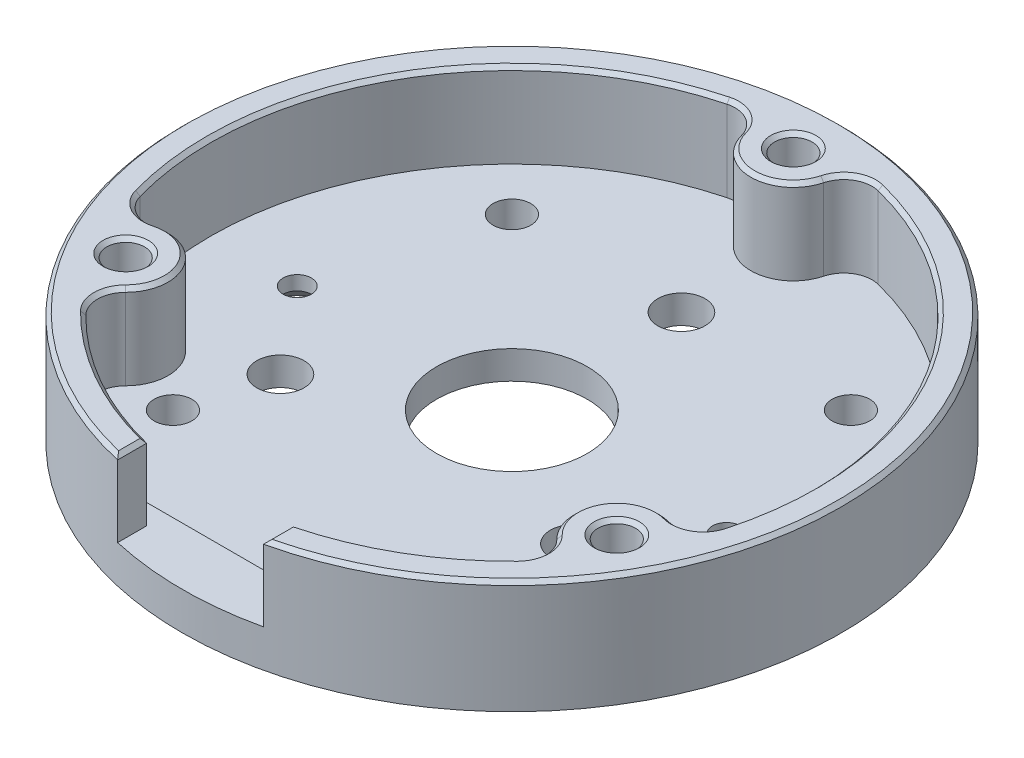
SolidWorks part; units mm, degrees
ref_plane "Спереди" through (0, 0, 0) normal (0, 0, 1) x (1, 0, 0)
ref_plane "Сверху" through (0, 0, 0) normal (0, 1, 0) x (1, 0, 0)
ref_plane "Справа" through (0, 0, 0) normal (1, 0, 0) x (0, 0, -1)
other "Configuration Table"
sketch "Эскиз1" plane through (0, 0, 0) normal (0, 1, 0) x (1, 0, 0)
  circle A0 centre (0, 0) radius 35
  circle A1 centre (0, 0) radius 8
  dimension "D1" = 16
  dimension "D2" = 70
extrude "Бобышка-Вытянуть1" add sketch "Эскиз1" along normal blind 3
sketch "Эскиз2" plane through (0, 3, 0) normal (0, 1, 0) x (1, 0, 0)
  circle A17 centre (-0.1137, 30) radius 2
  circle A18 centre (26.0376, -14.9016) radius 2
  circle A19 centre (-25.9239, -15.0984) radius 2
  circle A21 centre (0, 0) radius 35
  arc A22 (-8.1171, 30.9534) -> (-30.8001, -8.6807) centre (0, 0) ccw
  arc A23 (-4.4591, 28.8309) -> (4.2406, 28.8639) centre (-0.1137, 30) ccw
  arc A24 (27.1979, -10.5537) -> (22.8766, -18.1044) centre (26.0376, -14.9016) ccw
  arc A25 (-22.7387, -18.2772) -> (-27.1171, -10.7595) centre (-25.9239, -15.0984) ccw
  arc A26 (30.865, -8.4471) -> (7.8823, 31.014) centre (0, 0) ccw
  arc A27 (-22.7479, -22.5063) -> (22.9178, -22.3333) centre (0, 0) ccw
  arc A28 (-27.1171, -10.7595) -> (-30.8001, -8.6807) centre (-27.9126, -7.8669) cw
  arc A29 (-22.7387, -18.2772) -> (-22.7479, -22.5063) centre (-20.6153, -20.3964) ccw
  arc A30 (22.8766, -18.1044) -> (22.9178, -22.3333) centre (20.7692, -20.2396) cw
  arc A31 (27.1979, -10.5537) -> (30.865, -8.4471) centre (27.9714, -7.6552) ccw
  arc A32 (-8.1171, 30.9534) -> (-4.4591, 28.8309) centre (-7.3561, 28.0515) cw
  arc A33 (7.8823, 31.014) -> (4.2406, 28.8639) centre (7.1434, 28.1064) ccw
  point P12 (0, 0)
  point P16 (0, 0)
  point P18 (-25.327, -19.5587)
  point P23 (29.6018, -12.1545)
  point P45 (0, 0)
  dimension "D1" = 70
  dimension "D2" = 64
  dimension "D5" = 3
  dimension "D6" = 4
  dimension "D8" = 30
  dimension "D3" = 9
  dimension "D7" = 3
  dimension "D4" = 3
extrude "Бобышка-Вытянуть2" add sketch "Эскиз2" along normal blind 9
sketch "Эскиз3" plane through (0, 3, 0) normal (0, 1, 0) x (1, 0, 0)
  line L0 (0, 0) -> (0, 38.3083) construction
  line L2 (43.0111, 0) -> (0, 0) construction
  circle A0 centre (22.8, 0) radius 1.5
  circle A4 centre (-22.8, 0) radius 1.5
  circle A8 centre (0, 22.8) radius 1.5 [skipped]
  circle A9 centre (-16.122, 16.122) radius 1.5 [skipped]
  circle A10 centre (16.122, 16.122) radius 1.5 [skipped]
  circle A11 centre (-16.122, -16.122) radius 1.5 [skipped]
  circle A12 centre (0, -22.8) radius 1.5 [skipped]
  circle A13 centre (16.122, -16.122) radius 1.5 [skipped]
  point P15 (0, 0)
  dimension "D2" = 3
  dimension "D1" = 90
  dimension "D3" = 22.8
  dimension "D5" = 22.8
  dimension "D4" = 8
extrude "Вырез-Вытянуть1" cut sketch "Эскиз3" against normal blind 8
sketch "Эскиз4" plane through (0, 3, 0) normal (0, 1, 0) x (1, 0, 0)
  line L0 (0, 18) -> (0, 0) construction
  circle A0 centre (0, 18) radius 2.5064
  circle A1 centre (15.5885, -9) radius 2.5064
  circle A2 centre (-15.5885, -9) radius 2.5064
  point P15 (0, 0)
  dimension "D2" = 18
  dimension "D3" = 3
extrude "Вырез-Вытянуть2" cut sketch "Эскиз4" against normal blind 8
sketch "Эскиз5" plane through (0, 3, 0) normal (0, 1, 0) x (1, 0, 0)
  line L1 (-12.0085, 30.9047) -> (-30.9047, 12.0085)
  arc A0 (-30.9047, 12.0085) -> (-12.0085, 30.9047) centre (0, 0) cw
extrude "Бобышка-Вытянуть3" [suppressed] add sketch "Эскиз5" along normal blind 1
sketch "Эскиз7" plane through (0, 3, 0) normal (0, 1, 0) x (1, 0, 0)
  circle A0 centre (-18, -18) radius 2
  circle A1 centre (18, -18) radius 2
  circle A2 centre (-18, 18) radius 2
  circle A3 centre (18, 18) radius 2
  dimension "D1" = 4
  dimension "D2" = 4
  dimension "D5" = 4
  dimension "D6" = 4
  dimension "D3" = 18
  dimension "D4" = 18
  dimension "D7" = 18
  dimension "D8" = 18
  dimension "D9" = 18
  dimension "D10" = 18
extrude "Вырез-Вытянуть4" cut sketch "Эскиз7" against normal blind 12
sketch "Эскиз8" plane through (0, 3, 0) normal (0, 1, 0) x (1, 0, 0)
  line L0 (-13.7488, -28.8958) -> (13.7488, -28.8958)
  arc A0 (-22.7479, -22.5063) -> (22.9178, -22.3333) centre (0, 0) ccw construction
  arc A1 (-13.7488, -28.8958) -> (13.7488, -28.8958) centre (0, 0) ccw
extrude "Бобышка-Вытянуть4" add sketch "Эскиз8" along normal blind 1
sketch "Эскиз9" plane through (0, 0, 28.8958) normal (0, 0, -1) x (-1, 0, 0)
  line L0 (-13.7488, 4) -> (13.7488, 4) construction
  line L1 (-7.7488, 4) -> (7.7488, 4)
  line L2 (-7.7488, 4) -> (-7.7488, 13.4818)
  line L3 (-7.7488, 13.4818) -> (7.7488, 13.4818)
  line L4 (7.7488, 4) -> (7.7488, 13.4818)
  line L5 (13.7488, 4) -> (13.7488, 3) construction
  dimension "D1" = 6
  dimension "D2" = 6
  dimension "D3" = 15.4977
extrude "Вырез-Вытянуть5" cut sketch "Эскиз9" against normal blind 11
sketch "Эскиз10" plane through (0, 3, 0) normal (0, 1, 0) x (1, 0, 0)
  circle A0 centre (0, 0) radius 22.5 construction
  dimension "D1" = 45
chamfer "Фаска1" distance 0.4 angle 45 19 edges at (-25.9239, 12, 17.0984) (-0.1137, 12, -28) (26.0376, 12, 16.9016) (15.9403, 12, 27.7472) (23.7691, 12, 20.2103) (22.132, 12, 12.6663) (29.4658, 12, 10.2565) (27.652, 12, -16.1049) (5.6181, 12, -30.6898) (-0.0966, 12, -25.5) (-5.8505, 12, -30.6463) (-27.7732, 12, -15.8949) (-29.3872, 12, 10.4794) (-22.0354, 12, 12.8337) (-23.6152, 12, 20.3899) (-15.8351, 12, 27.8074) (-7.7488, 12, 32.5895) (0, 12, -35) (7.7488, 12, 32.5895)
chamfer "Фаска2" distance 1.5 angle 45 2 edges at (22.8, 0, 1.5) (-22.8, 0, 1.5)
equation "\"22б5\"=23.4905"
